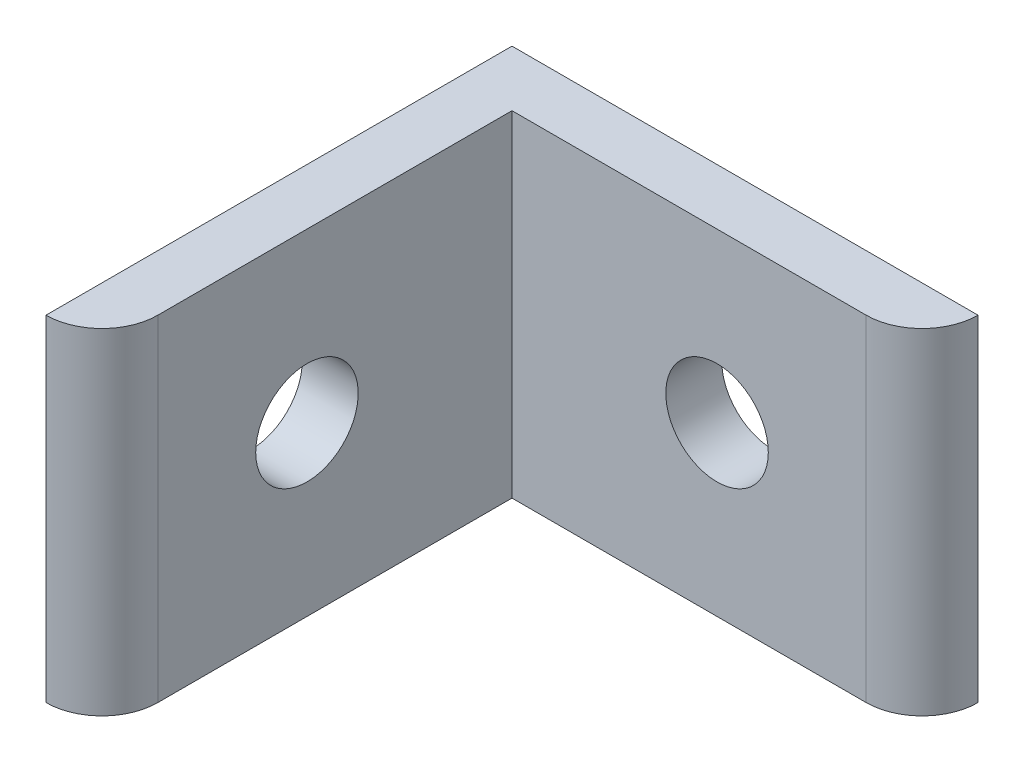
SolidWorks part; units mm, degrees
ref_plane "Front Plane" through (0, 0, 0) normal (1, 0, 0) x (0, 1, 0)
ref_plane "Top Plane" through (0, 0, 0) normal (0, 0, 1) x (0, 1, 0)
ref_plane "Right Plane" through (0, 0, 0) normal (0, 1, 0) x (-1, 0, 0)
sketch "Sketch2" plane through (0, 0, 0) normal (0, 1, 0) x (-1, 0, 0)
  line L0 (0, 0) -> (0, 25)
  line L1 (0, 0) -> (-25, 0)
  line L2 (-25, 0) -> (-25, 3)
  line L3 (-25, 3) -> (-3, 3)
  line L4 (-3, 3) -> (-3, 25)
  line L5 (-3, 25) -> (0, 25)
  dimension "D1" = 3
  dimension "D2" = 3
  dimension "D3" = 25
  dimension "D4" = 25
extrude "Boss-Extrude1" add sketch "Sketch2" along normal blind 18
sketch "Sketch3" plane through (0, 0, 3) normal (0, 0, 1) x (1, 0, 0)
  line L1 (3, 0) -> (25, 0)
  line L2 (3, 0) -> (3, 18)
  line L3 (3, 18) -> (25, 18)
  line L4 (25, 0) -> (25, 18)
  line L5 (3, 0) -> (25, 18) construction
  line L6 (3, 18) -> (25, 0) construction
  circle A0 centre (14, 9) radius 2.75
  point P4 (14, 9)
  dimension "D1" = 5.5
extrude "Cut-Extrude2" cut sketch "Sketch3" against normal through all contours A0
ref_plane "Plane1" through (0, 0, 0) normal (-0.7071, 0, 0.7071) x (0, -1, 0)
mirror "Mirror1" about plane through (0, 0, 0) normal (-0.7071, 0, 0.7071) of "Cut-Extrude2"
fillet "Fillet1" radius 3 2 edges at (3, 9, 25) (25, 9, 3)
